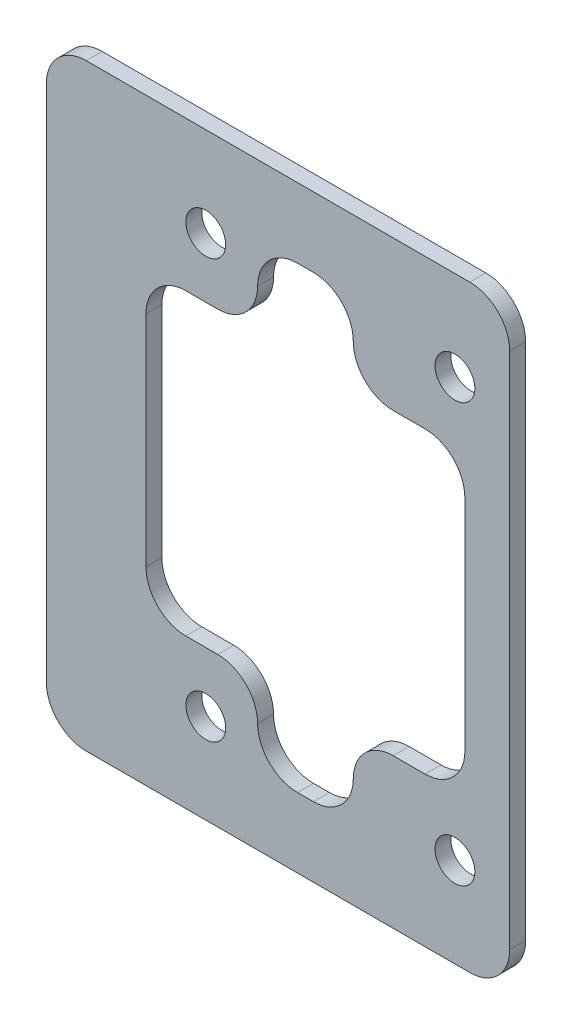
SolidWorks part; units mm, degrees
ref_plane "Front Plane" through (0, 0, 0) normal (0, 0, 1) x (1, 0, 0)
ref_plane "Top Plane" through (0, 0, 0) normal (0, 1, 0) x (1, 0, 0)
ref_plane "Right Plane" through (0, 0, 0) normal (1, 0, 0) x (0, 0, -1)
sketch "Sketch1" plane through (0, 0, 0) normal (0, 0, 1) x (1, 0, 0)
  line L0 (25.6874, 35) -> (13.1874, 35) construction
  line L1 (5.1874, 39.5) -> (28.4374, 39.5)
  line L2 (5.1874, 39.5) -> (5.1874, 9.5)
  line L3 (5.1874, 9.5) -> (28.4374, 9.5)
  line L4 (28.4374, 39.5) -> (28.4374, 9.5)
  line L5 (25.6874, 14) -> (13.1874, 14) construction
  line L6 (19.4374, 35) -> (19.4374, 14) construction
  line L7 (28.4374, 24.5) -> (5.1874, 24.5) construction
  circle A0 centre (25.6874, 14) radius 1
  circle A1 centre (25.6874, 35) radius 1
  circle A2 centre (13.1874, 14) radius 1
  circle A3 centre (13.1874, 35) radius 1
  point P4 (25.6874, 35)
  point P5 (13.1874, 35)
  point P7 (13.1874, 14)
  point P9 (25.6874, 14)
  point P22 (19.4374, 24.5)
  point P24 (28.4374, 24.5)
  dimension "D4" = 2
  dimension "D1" = 30
  dimension "D2" = 8
  dimension "D3" = 2.75
extrude "body" add sketch "Sketch1" along normal blind 0.8
fillet "corner fillet" radius 2 4 edges at (5.1874, 9.5, 0.4) (28.4374, 9.5, 0.4) (5.1874, 39.5, 0.4) (28.4374, 39.5, 0.4)
sketch "Sketch2" plane through (0, 0, 0) normal (0, 0, -1) x (-1, 0, 0)
  line L1 (-26.1874, 17) -> (-26.1874, 32)
  line L2 (-26.1874, 32) -> (-20.5874, 32)
  line L3 (-20.5874, 32) -> (-20.5874, 36)
  line L4 (-20.5874, 36) -> (-15.7874, 36)
  line L5 (-15.7874, 36) -> (-15.7874, 32)
  line L6 (-15.7874, 32) -> (-10.1874, 32)
  line L7 (-10.1874, 32) -> (-10.1874, 17)
  line L8 (-18.1874, 13) -> (-18.1874, 36) construction
  line L9 (-10.1874, 24.5) -> (-26.1874, 24.5) construction
  line L10 (-28.4374, 24.5) -> (-5.1874, 24.5) construction
  line L11 (-15.7874, 17) -> (-10.1874, 17)
  line L12 (-15.7874, 13) -> (-15.7874, 17)
  line L13 (-20.5874, 13) -> (-15.7874, 13)
  line L14 (-20.5874, 17) -> (-20.5874, 13)
  line L15 (-26.1874, 17) -> (-20.5874, 17)
  dimension "D1" = 5
  dimension "D2" = 16
  dimension "D3" = 4.8
  dimension "D4" = 11.5
  dimension "D5" = 15
extrude "cutout" cut sketch "Sketch2" against normal through all
fillet "cutout fillet" radius 2 12 edges at (26.1874, 32, 0.4) (20.5874, 32, 0.4) (20.5874, 36, 0.4) (15.7874, 36, 0.4) (15.7874, 32, 0.4) (10.1874, 32, 0.4) (10.1874, 17, 0.4) (15.7874, 17, 0.4) (15.7874, 13, 0.4) (20.5874, 13, 0.4) (20.5874, 17, 0.4) (26.1874, 17, 0.4)
